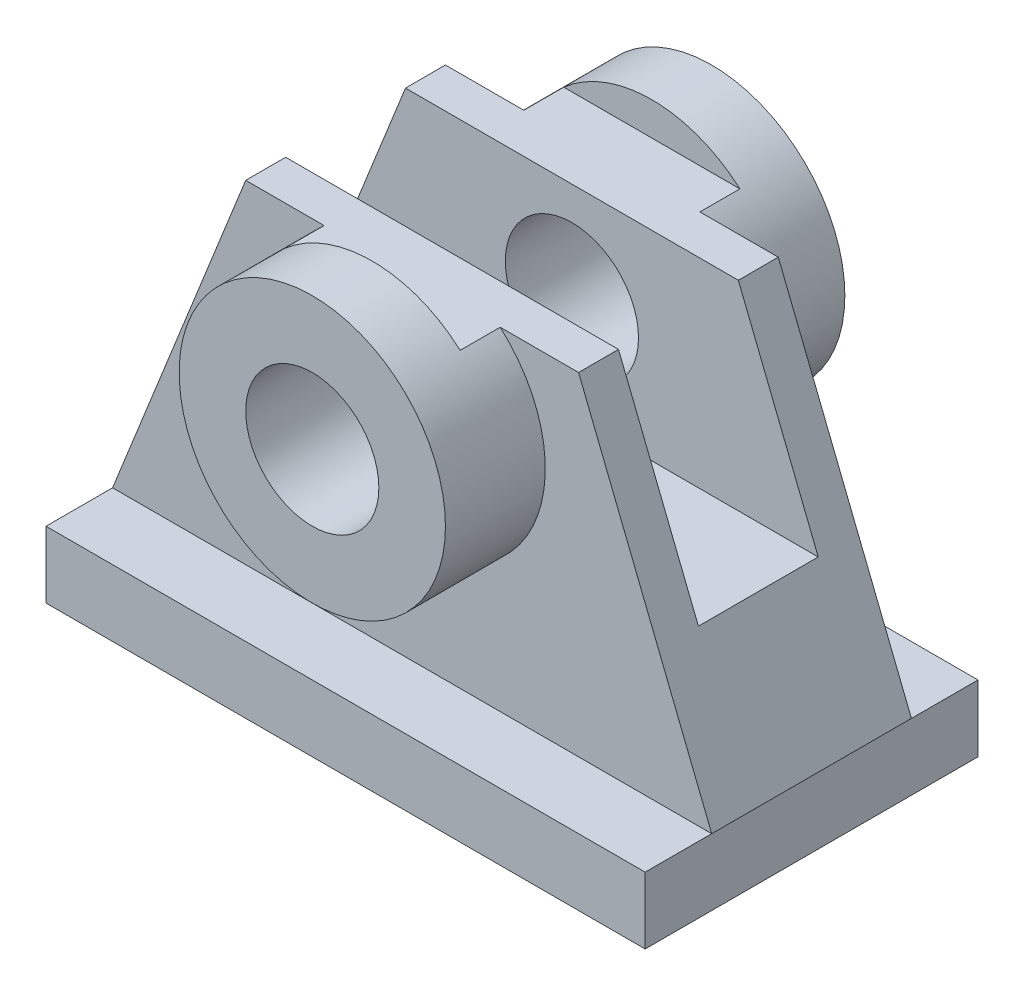
SolidWorks part; units mm, degrees
ref_plane "Front Plane" through (0, 0, 0) normal (0, 0, 1) x (1, 0, 0)
ref_plane "Top Plane" through (0, 0, 0) normal (0, 1, 0) x (1, 0, 0)
ref_plane "Right Plane" through (0, 0, 0) normal (1, 0, 0) x (0, 0, -1)
sketch "Sketch1" plane through (0, 0, 0) normal (0, 0, 1) x (1, 0, 0)
  line L0 (0, 0) -> (-5168.529, 0) construction
  line L1 (0, 0) -> (0, -5168.529) construction
  line L2 (-45, 0) -> (-25, 50)
  line L3 (45, -10) -> (-45, -10)
  line L4 (45, -10) -> (45, 0)
  line L5 (45, 0) -> (-45, 0)
  line L6 (-45, -10) -> (-45, 0)
  line L7 (0, 0) -> (0, -10) construction
  line L8 (45, -5) -> (-45, -5) construction
  line L9 (-25, 50) -> (25, 50)
  line L10 (25, 50) -> (45, 0)
  circle A0 centre (0, 35) radius 10
  circle A1 centre (0, 35) radius 20
  point P5 (0, -5)
  point P11 (0, 50)
  dimension "D5" = 20
  dimension "D6" = 40
  dimension "D1" = 10
  dimension "D2" = 90
  dimension "D3" = 50
  dimension "D4" = 50
  dimension "D7" = 45
extrude "Boss-Extrude1" add sketch "Sketch1" along normal mid plane 50 contours L6 L3 L4 L5 region at (0, -5, 0)
extrude "Boss-Extrude2" add sketch "Sketch1<3>" along normal blind 6 from offset 9 contours A1 L9 L2 L5 L10 | L9 A1 A0 | A0 region at (-34.0441, 24.6176, 0) region at (0, 49.4685, 0) region at (0, 35, 0)
sketch "Sketch1<3>" plane through (0, 0, 0) normal (0, 0, 1) x (1, 0, 0) same geometry as "Sketch1"
mirror "Mirror1" about plane through (0, 0, 0) normal (0, 0, 1) of "Boss-Extrude2"
extrude "Boss-Extrude3" add sketch "Sketch1<4>" along normal blind 15 from offset 15 contours L9 A1 A0 | L9 A1 region at (0, 52.0231, 0) region at (0, 49.4685, 0)
sketch "Sketch1<4>" plane through (0, 0, 0) normal (0, 0, 1) x (1, 0, 0) same geometry as "Sketch1"
mirror "Mirror2" about plane through (0, 0, 0) normal (0, 0, 1) of "Boss-Extrude3"
extrude "Cut-Extrude1" cut sketch "Sketch1<5>" against normal mid plane 95 contours A0 region at (0, 35, 0)
sketch "Sketch1<5>" plane through (0, 0, 0) normal (0, 0, 1) x (1, 0, 0) same geometry as "Sketch1"
sketch "Sketch2" plane through (-45, 0, 0) normal (-1, 0, 0) x (0, 0, 1)
  line L0 (0, 0) -> (0, -50000) construction
  line L1 (0, 0) -> (-50000, 0) construction
  line L2 (-21, 50) -> (21, 50)
  line L3 (-15, 50) -> (-9, 50) construction
  line L4 (15, 50) -> (9, 50) construction
  line L5 (-21, 50) -> (-21, 65)
  line L6 (-21, 65) -> (21, 65)
  line L7 (21, 65) -> (21, 50)
  point P12 (0, 50)
  dimension "D1" = 42
  dimension "D2" = 15
extrude "Cut-Extrude2" cut sketch "Sketch2" against normal through all
sketch "Sketch3" plane through (0, 0, -15) normal (0, 0, -1) x (-1, 0, 0)
  line L0 (-45, 0) -> (-37, 20)
  line L1 (-25, 50) -> (-45, 0) construction
  line L2 (-37, 20) -> (37, 20)
  line L3 (45, 0) -> (25, 50) construction
  line L4 (37, 20) -> (45, 0)
  line L5 (45, 0) -> (-45, 0)
  line L6 (-13.2288, 50) -> (-25, 50) construction
  dimension "D1" = 30
extrude "Boss-Extrude4" add sketch "Sketch3" against normal up to surface (24 mm away) from offset 6 up to face at (10, 35, 9) offset against normal yes
